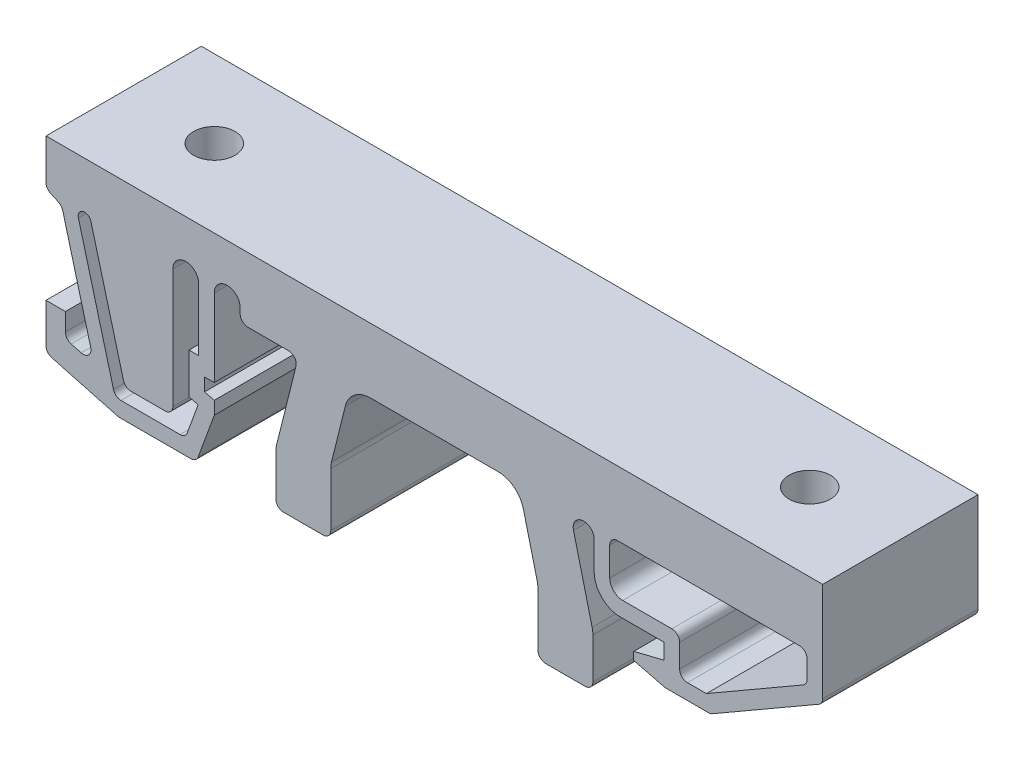
SolidWorks part; units mm, degrees
material "ABS"
ref_plane "Front Plane" through (0, 0, 0) normal (0, 0, 1) x (1, 0, 0)
ref_plane "Top Plane" through (0, 0, 0) normal (0, 1, 0) x (1, 0, 0)
ref_plane "Right Plane" through (0, 0, 0) normal (1, 0, 0) x (0, 0, -1)
sketch "Sketch2" plane through (0, 0, 0) normal (0, 0, 1) x (1, 0, 0)
  line L0 (0, 22.5226) -> (0, -8.8845) construction
  line L1 (6.5, 11) -> (-6.5, 11)
  line L2 (-6.5, 11) -> (-8, 4.9838)
  line L3 (-8, 4.9838) -> (-8, 0)
  line L4 (-8, 0) -> (-12.25, 0)
  line L5 (-12.25, 0) -> (-12.25, 3.9811)
  line L6 (-12.25, 3.9811) -> (-10.5, 11)
  line L7 (-10.5, 11) -> (-15, 11)
  line L8 (-15, 11) -> (-15, 13)
  line L9 (-15, 13) -> (-17, 13)
  line L10 (-17, 13) -> (-17, 6)
  line L11 (-17, 6) -> (-17.75, 6)
  line L12 (-17.75, 6) -> (-17.75, 5)
  line L13 (-17.75, 5) -> (-17, 4.813)
  line L14 (-17, 4.813) -> (-17, 3.813)
  line L15 (-17, 3.813) -> (-18.3878, 0)
  line L16 (-18.3878, 0) -> (-24.3878, 0)
  line L17 (-24.3878, 0) -> (-30, 1.5038)
  line L18 (-30, 1.5038) -> (-30, 5.0038)
  line L19 (-30, 5.0038) -> (-28.5, 5.0038)
  line L20 (-28.5, 5.0038) -> (-28.5, 3.1724)
  line L21 (-28.5, 3.1724) -> (-26.2784, 2.5771)
  line L22 (-26.2784, 2.5771) -> (-28.7854, 11.9336)
  line L23 (-28.7854, 11.9336) -> (-30, 12.5)
  line L24 (-30, 12.5) -> (-30, 16)
  line L25 (-30, 16) -> (0, 16)
  line L30 (-8, 0) -> (0, 0) construction
  line L32 (10.5, 11) -> (12.35, 11)
  line L33 (12.25, 3.9811) -> (10.5, 11)
  line L34 (12.25, 0) -> (12.25, 3.9811)
  line L35 (8, 0) -> (12.25, 0)
  line L36 (8, 4.9838) -> (8, 0)
  line L37 (6.5, 11) -> (8, 4.9838)
  line L38 (12.35, 11) -> (12.35, 6)
  line L40 (12.35, 6) -> (17.75, 6)
  line L41 (17.75, 6) -> (17.75, 4.8)
  line L42 (17.75, 4.8) -> (15.4, 4.2141)
  line L43 (15.4, 4.2141) -> (15.4, 3.6083)
  line L44 (15.4, 3.6083) -> (17.8397, 3)
  line L45 (17.8397, 3) -> (21.3397, 3)
  line L46 (21.3397, 3) -> (30, 8)
  line L47 (30, 8) -> (30, 16)
  line L48 (30, 16) -> (0, 16)
  line L49 (-17.75, 6) -> (0, 6) construction
  line L50 (0, 6) -> (17.75, 6) construction
  line L54 (15.4, 3.9112) -> (22.918, 3.9112) construction
  line L56 (-8, 0) -> (8, 0) construction
  point P37 (0, 11)
  dimension "D1" = 5
  dimension "D2" = 16
  dimension "D3" = 104
  dimension "D4" = 16
  dimension "D5" = 13
  dimension "D6" = 24.5
  dimension "D7" = 4
  dimension "D8" = 2
  dimension "D9" = 2
  dimension "D10" = 4.5
  dimension "D11" = 35.5
  dimension "D12" = 7
  dimension "D13" = 1
  dimension "D14" = 1
  dimension "D15" = 20
  dimension "D16" = 6
  dimension "D17" = 15
  dimension "D18" = 1.5
  dimension "D19" = 3.5
  dimension "D20" = 2
  dimension "D21" = 60
  dimension "D22" = 60
  dimension "D23" = 50
  dimension "D24" = 3.5
  dimension "D25" = 2.3
  dimension "D26" = 60
  dimension "D27" = 8
  dimension "D28" = 15.4
  dimension "D29" = 3.5
  dimension "D30" = 1.2
  dimension "D31" = 5.4
  dimension "D32" = 3
extrude "Boss-Extrude1" add sketch "Sketch2" along normal mid plane 12
sketch "Sketch3" plane through (0, 0, 0) normal (0, 0, 1) x (1, 0, 0)
  line L0 (-27.6263, 12.2442) -> (-24.667, 1.2)
  line L1 (-24.667, 1.2) -> (-19.2281, 1.2)
  line L2 (-19.2281, 1.2) -> (-18.2498, 3.8879)
  line L3 (-18.2498, 3.8879) -> (-18.95, 4.0625)
  line L4 (-18.95, 4.0625) -> (-18.95, 7.2)
  line L5 (-18.95, 7.2) -> (-18.2, 7.2)
  line L6 (-18.2, 7.2) -> (-18.2, 13)
  line L7 (-18.2, 13) -> (-20.2, 13)
  line L8 (-20.2, 13) -> (-20.2, 2.2)
  line L9 (-20.2, 2.2) -> (-23.8997, 2.2)
  line L10 (-23.8997, 2.2) -> (-26.6604, 12.503)
  line L11 (-26.6604, 12.503) -> (-27.6263, 12.2442)
  line L12 (13.55, 11) -> (13.55, 7.2)
  line L13 (13.55, 7.2) -> (18.95, 7.2)
  line L14 (18.95, 7.2) -> (18.95, 4.2)
  line L15 (18.95, 4.2) -> (21.0182, 4.2)
  line L16 (21.0182, 4.2) -> (28.8, 8.6928)
  line L17 (28.8, 8.6928) -> (28.8, 11)
  line L18 (28.8, 11) -> (13.55, 11)
  line L19 (-28.7854, 11.9336) -> (-26.2784, 2.5771) construction
  line L20 (-18.3878, 0) -> (-17, 3.813) construction
  line L21 (-24.3878, 0) -> (-18.3878, 0) construction
  line L22 (-17.75, 5) -> (-17.75, 6) construction
  line L23 (-17, 6) -> (-17, 13) construction
  line L26 (-17, 4.813) -> (-17.75, 5) construction
  line L27 (-17.75, 6) -> (-17, 6) construction
  line L28 (-17, 13) -> (-15, 13) construction
  line L29 (12.35, 11) -> (12.35, 6) construction
  line L30 (12.35, 6) -> (17.75, 6) construction
  line L31 (17.75, 6) -> (17.75, 4.8) construction
  line L32 (30, 8) -> (30, 16) construction
  line L33 (21.3397, 3) -> (30, 8) construction
  line L34 (17.8397, 3) -> (21.3397, 3) construction
  line L35 (10.5, 11) -> (12.35, 11) construction
  dimension "D1" = 1.2
  dimension "D2" = 1.2
  dimension "D3" = 1.2
  dimension "D4" = 1.2
  dimension "D5" = 1.2
  dimension "D6" = 2
  dimension "D7" = 1
  dimension "D8" = 1.2
  dimension "D9" = 1.2
  dimension "D10" = 1.2
  dimension "D11" = 1.2
  dimension "D12" = 1.2
  dimension "D13" = 1.2
  dimension "D14" = 1.2
  dimension "D15" = 1.2
  dimension "D16" = 1
extrude "Cut-Extrude1" cut sketch "Sketch3" against normal through all both and the other way through all
fillet "Fillet1" radius 2 1 edges at (12.35, 6, 0)
fillet "Fillet2" radius 1 1 edges at (13.55, 7.2, 0)
fillet "Fillet3" 2 edges at (10.5, 11, 0) (12.35, 11, 0) type full round first side face at (11.375, 7.4906, 0) second side face at (12.35, 9.5, 0) middle face at (11.425, 11, 0)
fillet "Fillet4" radius 2 6 edges at (-12.25, 3.9811, 0) (12.25, 3.9811, 0) (8, 4.9838, 0) (-8, 4.9838, 0) (-6.5, 11, 0) (6.5, 11, 0)
fillet "Fillet5" 2 edges at (-20.2, 13, 0) (-18.2, 13, 0) type full round first side face at (-20.2, 7.6, 0) second side face at (-18.2, 10.1, 0) middle face at (-19.2, 13, 0)
fillet "Fillet6" 2 edges at (-17, 13, 0) (-15, 13, 0) type full round first side face at (-17, 9.5, 0) second side face at (-15, 12, 0) middle face at (-16, 13, 0)
fillet "Fillet7" 2 edges at (-27.6263, 12.2442, 0) (-26.6604, 12.503, 0) type full round first side face at (-26.1467, 6.7221, 0) second side face at (-25.2801, 7.3515, 0) middle face at (-27.1434, 12.3736, 0)
fillet "Fillet8" radius 0.6 25 edges at (-10.5, 11, 0) (-12.25, 0, 0) (-8, 0, 0) (8, 0, 0) (12.25, 0, 0) (17.8397, 3, 0) (28.8, 8.6928, 0) (28.8, 11, 0) (13.55, 11, 0) (18.95, 7.2, 0) (18.95, 4.2, 0) (21.3397, 3, 0) (30, 8, 0) (-23.8997, 2.2, 0) (-20.2, 2.2, 0) (-30, 1.5038, 0) (-28.5, 3.1724, 0) (-26.2784, 2.5771, 0) (-24.667, 1.2, 0) (-19.2281, 1.2, 0) (-24.3878, 0, 0) (-18.3878, 0, 0) (-15, 11, 0) (-30, 12.5, 0) (-28.7854, 11.9336, 0)
sketch "Sketch4" plane through (0, 16, 0) normal (0, 1, 0) x (1, 0, 0)
  line L0 (0, 0) -> (-23, 0) construction
  line L3 (0, 0) -> (0, -6) construction
  line L4 (30, -6) -> (-30, -6) construction
  circle A0 centre (-23, 0) radius 1.6
  circle A1 centre (23, 0) radius 1.6
  dimension "D1" = 3.2
  dimension "D2" = 46
extrude "Cut-Extrude2" cut sketch "Sketch4" against normal blind 8.5
